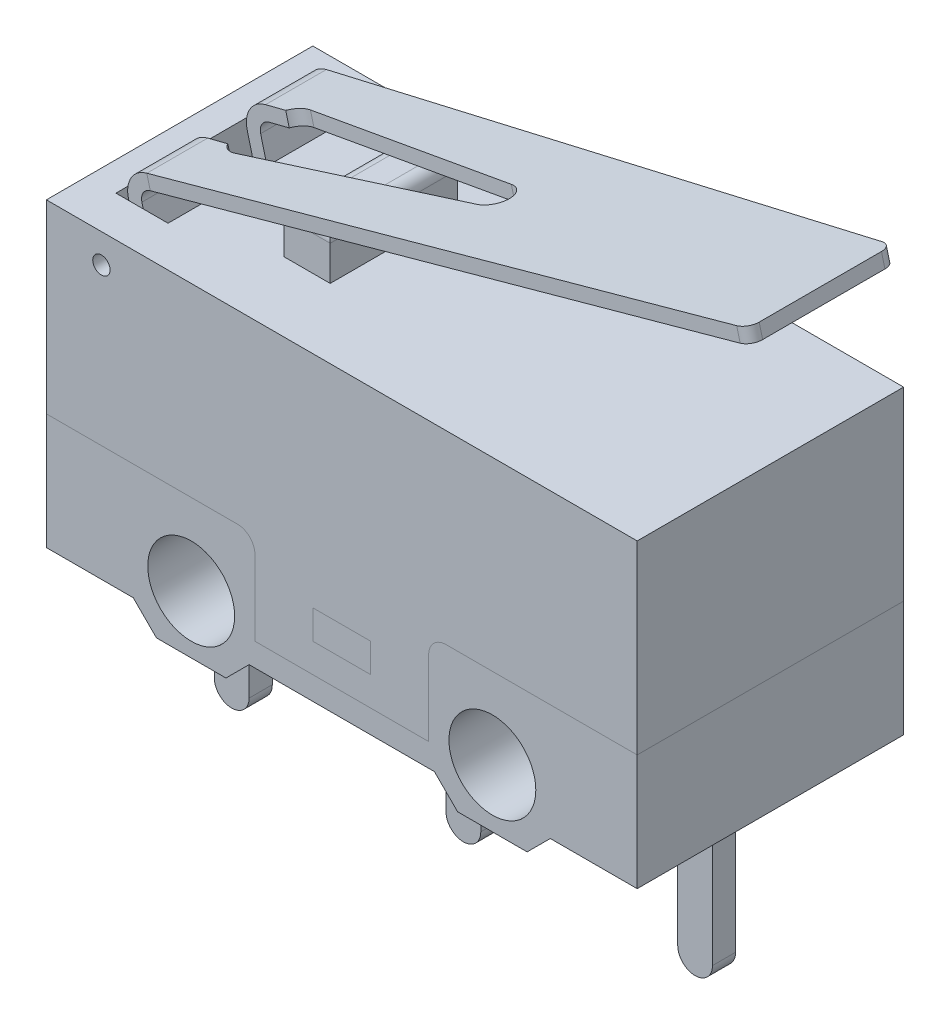
SolidWorks part; units mm, degrees
ref_plane "Front Plane" through (0, 0, 0) normal (0, 0, 1) x (1, 0, 0)
ref_plane "Top Plane" through (0, 0, 0) normal (0, 1, 0) x (1, 0, 0)
ref_plane "Right Plane" through (0, 0, 0) normal (1, 0, 0) x (0, 0, -1)
sketch "Sketch1" plane through (0, 0, 0) normal (0, 0, 1) x (1, 0, 0)
  line L0 (-4.572, -3.302) -> (-4.064, -3.81)
  line L1 (-6.477, 3.302) -> (6.477, 3.302)
  line L2 (-6.477, 3.302) -> (-6.477, -3.302)
  line L3 (-6.477, -3.302) -> (-4.572, -3.302)
  line L4 (6.477, 3.302) -> (6.477, -3.302)
  line L5 (-6.477, 3.302) -> (6.477, -3.302) construction
  line L6 (-6.477, -3.302) -> (6.477, 3.302) construction
  line L7 (-4.064, -3.81) -> (-2.54, -3.81)
  line L8 (-2.54, -3.81) -> (-2.032, -3.302)
  line L9 (2.032, -3.302) -> (2.54, -3.81)
  line L10 (2.54, -3.81) -> (4.064, -3.81)
  line L11 (4.064, -3.81) -> (4.572, -3.302)
  line L12 (0, 0) -> (0, -3.302) construction
  line L13 (-2.032, -3.302) -> (2.032, -3.302)
  line L14 (4.572, -3.302) -> (6.477, -3.302)
  line L15 (-3.302, -3.81) -> (-3.302, -3.302) construction
  line L16 (3.302, -3.81) -> (3.302, -3.302) construction
  circle A0 centre (3.302, -2.54) radius 0.9525
  circle A1 centre (-3.302, -2.54) radius 0.9525
  point P0 (0, 0)
  point P18 (-3.302, -3.81)
  point P19 (3.302, -3.81)
  dimension "D6" = 1.905
  dimension "D1" = 12.954
  dimension "D2" = 6.604
  dimension "D3" = 6.604
  dimension "D4" = 0.508
  dimension "D5" = 2.54
  dimension "D7" = 1.27
extrude "Boss-Extrude1" add sketch "Sketch1" along normal mid plane 5.842
sketch "Sketch2" plane through (0, 0, 2.921) normal (0, 0, 1) x (1, 0, 0)
  line L0 (-6.477, -0.762) -> (-2.286, -0.762)
  line L1 (-6.477, 3.302) -> (-6.477, -3.302) construction
  line L2 (-1.905, -1.143) -> (-1.905, -2.794)
  line L3 (-1.905, -2.794) -> (1.905, -2.794)
  line L4 (1.905, -2.794) -> (1.905, -1.143)
  line L5 (2.286, -0.762) -> (6.477, -0.762)
  line L6 (6.477, -3.302) -> (6.477, 3.302) construction
  line L7 (0, 0) -> (0, -2.794) construction
  line L8 (-6.477, -3.302) -> (-4.572, -3.302) construction
  line L9 (-2.032, -3.302) -> (2.032, -3.302) construction
  line L11 (-0.635, -1.524) -> (0.635, -1.524)
  line L12 (-0.635, -1.524) -> (-0.635, -2.159)
  line L13 (-0.635, -2.159) -> (0.635, -2.159)
  line L14 (0.635, -1.524) -> (0.635, -2.159)
  line L15 (-0.635, -1.524) -> (0.635, -2.159) construction
  line L16 (-0.635, -2.159) -> (0.635, -1.524) construction
  arc A0 (1.905, -1.143) -> (2.286, -0.762) centre (2.286, -1.143) cw
  arc A1 (-2.286, -0.762) -> (-1.905, -1.143) centre (-2.286, -1.143) cw
  point P22 (0, -1.8415)
  dimension "D4" = 0.381
  dimension "D1" = 2.54
  dimension "D2" = 0.508
  dimension "D3" = 3.81
  dimension "D5" = 1.27
  dimension "D6" = 0.635
  dimension "D7" = 0.635
split line "Split Line1"
sketch "Sketch3" plane through (6.477, 0, 0) normal (1, 0, 0) x (0, 0, -1)
  line L0 (-2.921, -0.762) -> (2.921, -0.762)
split line "Split Line2"
sketch "Sketch4" plane through (0, -3.302, 0) normal (0, -1, 0) x (1, 0, 0)
  line L0 (0, 0) -> (0, -0.254) construction
  line L1 (-5.461, 0.254) -> (-4.699, 0.254)
  line L2 (-5.461, 0.254) -> (-5.461, -0.254)
  line L3 (-5.461, -0.254) -> (-4.699, -0.254)
  line L4 (-4.699, 0.254) -> (-4.699, -0.254)
  line L5 (-5.461, 0.254) -> (-4.699, -0.254) construction
  line L6 (-5.461, -0.254) -> (-4.699, 0.254) construction
  line L7 (-0.381, 0.254) -> (0.381, 0.254)
  line L8 (-0.381, 0.254) -> (-0.381, -0.254)
  line L9 (-0.381, -0.254) -> (0.381, -0.254)
  line L10 (0.381, 0.254) -> (0.381, -0.254)
  line L11 (-0.381, 0.254) -> (0.381, -0.254) construction
  line L12 (-0.381, -0.254) -> (0.381, 0.254) construction
  line L13 (4.699, 0.254) -> (5.461, 0.254)
  line L14 (4.699, 0.254) -> (4.699, -0.254)
  line L15 (4.699, -0.254) -> (5.461, -0.254)
  line L16 (5.461, 0.254) -> (5.461, -0.254)
  line L17 (4.699, 0.254) -> (5.461, -0.254) construction
  line L18 (4.699, -0.254) -> (5.461, 0.254) construction
  point P0 (-5.08, 0)
  point P5 (0, 0)
  point P11 (5.08, 0)
  dimension "D1" = 0.762
  dimension "D2" = 0.508
  dimension "D3" = 10.16
extrude "Boss-Extrude2" add sketch "Sketch4" along normal blind 3.683
fillet "Fillet1" radius 0.381
sketch "Sketch5" plane through (0, 3.302, 0) normal (0, 1, 0) x (1, 0, 0)
  line L0 (-6.477, -2.921) -> (-6.477, 2.921) construction
  line L1 (-4.699, -2.032) -> (-5.842, -2.032)
  line L2 (-4.699, -2.032) -> (-4.699, 2.032)
  line L3 (-4.699, 2.032) -> (-5.842, 2.032)
  line L4 (-5.842, -2.032) -> (-5.842, 2.032)
  line L5 (-4.699, -2.032) -> (-5.842, 2.032) construction
  line L6 (-4.699, 2.032) -> (-5.842, -2.032) construction
  point P0 (-5.2705, 0)
  dimension "D1" = 1.143
  dimension "D2" = 4.064
  dimension "D3" = 0.635
extrude "Cut-Extrude1" cut sketch "Sketch5" against normal blind 1.27
sketch "Sketch7" plane through (0, 0, 0) normal (0, 0, 1) x (1, 0, 0)
  line L0 (-4.699, 3.302) -> (-5.842, 2.032) construction
  circle A0 centre (-5.2705, 2.667) radius 0.1905
  dimension "D1" = 0.381
extrude "Cut-Extrude2" cut sketch "Sketch7" against normal through all both and the other way through all
sketch "Sketch8" plane through (0, 0, 0) normal (0, 0, 1) x (1, 0, 0)
  line L0 (-2.794, 4.318) -> (-2.794, 3.302)
  line L1 (6.477, 3.302) -> (-6.477, 3.302) construction
  line L2 (-2.794, 3.302) -> (-1.778, 3.302)
  line L3 (-1.778, 3.302) -> (-1.778, 4.318)
  line L5 (-2.794, 4.318) -> (-1.778, 4.318)
  dimension "D1" = 1.016
  dimension "D2" = 3.683
  dimension "D3" = 1.016
extrude "Boss-Extrude3" add sketch "Sketch8" along normal mid plane 2.794 separate body
fillet "Fillet2" radius 0.254 4 edges at (-1.778, 4.318, 0) (-2.286, 4.318, 1.397) (-2.794, 4.318, 0) (-2.286, 4.318, -1.397)
sketch "Sketch9" plane through (0, 0, 0) normal (0, 0, 1) x (1, 0, 0)
  line L0 (-5.1285, 2.54) -> (-5.3353, 3.3523)
  line L1 (-5.1518, 3.6611) -> (7.6478, 6.92)
  line L2 (6.477, 3.302) -> (6.477, 6.6219) construction
  line L3 (-5.2705, 2.4765) -> (-5.2705, 2.667) construction
  line L4 (-5.2705, 2.54) -> (-5.1285, 2.54) construction
  circle A0 centre (-5.2705, 2.667) radius 0.1905 construction
  arc A2 (-2.54, 4.318) -> (-2.794, 4.064) centre (-2.54, 4.064) ccw construction
  arc A3 (-5.3353, 3.3523) -> (-5.1518, 3.6611) centre (-5.0892, 3.415) cw
  point P14 (-5.398, 3.5984)
  point P17 (-5.2705, 2.667)
  point P18 (-5.398, 3.5984)
  dimension "D3" = 0.254
  dimension "D1" = 1.0922
  dimension "D2" = 13.462
  dimension "D4" = 3.3199
  dimension "D5" = 0.0635
extrude "Extrude-Thin1" add sketch "Sketch9" along normal mid plane 4.826 separate body thin contours L0 A3 L1
ref_plane "Plane1" through (-0.9916, 3.8947, 0) normal (0.2467, -0.9691, 0) x (-0.9691, -0.2467, 0)
sketch "Sketch10" plane through (-0.9916, 3.8947, 0) normal (0.2467, -0.9691, 0) x (-0.9691, -0.2467, 0)
  line L0 (4.648, 1.9685) -> (4.0892, 1.9685)
  line L1 (4.0892, 1.9685) -> (-9.1188, 1.5875)
  line L2 (-9.1188, 1.5875) -> (-9.1188, -1.5875) construction
  line L3 (-9.1188, -1.5875) -> (4.0892, -1.9685)
  line L4 (4.648, -2.413) -> (4.648, 2.413) construction
  line L5 (4.0892, 2.413) -> (-9.1188, 2.413) construction
  line L6 (-9.1188, -2.413) -> (-9.1188, 2.413) construction
  line L8 (4.648, 2.413) -> (-9.1188, 2.413)
  line L9 (4.648, -2.413) -> (4.648, -1.9685)
  line L10 (-9.1188, -2.413) -> (4.648, -2.413)
  line L12 (4.0892, -1.9685) -> (4.648, -1.9685)
  line L13 (0, 0) -> (-9.1188, 0) construction
  line L15 (4.648, 1.9685) -> (4.648, 2.413)
  line L17 (4.0892, -2.413) -> (4.0892, 2.413) construction
  line L19 (4.648, -0.635) -> (3.632, -0.635)
  line L20 (3.632, -0.635) -> (3.632, 0.635) construction
  line L21 (3.632, 0.635) -> (4.648, 0.635)
  line L22 (4.648, 0) -> (0, 0) construction
  line L23 (3.2684, 0.824) -> (-1.7357, 0.3795)
  line L24 (3.2684, -0.824) -> (-1.7357, -0.3795)
  line L25 (-9.1188, 1.5875) -> (-9.1188, 2.413)
  line L26 (-9.1188, -1.5875) -> (-9.1188, -2.413)
  line L27 (4.648, 0.635) -> (4.648, -0.635)
  arc A0 (-1.7357, 0.3795) -> (-1.7357, -0.3795) centre (-1.702, 0) ccw
  arc A1 (3.632, 0.635) -> (3.2684, 0.824) centre (3.3021, 0.4445) ccw
  arc A2 (3.2684, -0.824) -> (3.632, -0.635) centre (3.3021, -0.4445) ccw
  dimension "D7" = 0.381
  dimension "D2" = 3.937
  dimension "D3" = 3.175
  dimension "D4" = 1.27
  dimension "D5" = 6.35
  dimension "D6" = 1.016
  dimension "D8" = 0.889
extrude "Cut-Extrude3" cut sketch "Sketch10" against normal blind 4.826
sketch "Sketch12" plane through (-0.9916, 3.8947, 0) normal (-0.2467, 0.9691, 0) x (0.9691, 0.2467, 0)
  line L4 (-4.3432, 0.635) -> (-4.648, 0.635)
  line L5 (-4.648, 0.635) -> (-4.648, -0.635)
  line L6 (-4.648, -0.635) -> (-4.3432, -0.635)
  line L8 (-4.3432, 0.635) -> (-4.648, 0.635)
  line L10 (-4.648, -0.635) -> (-4.3432, -0.635)
  line L18 (-4.3432, -0.635) -> (-4.3432, 0.635)
  line L19 (-4.3432, -0.635) -> (-4.3432, 0.635)
  line L21 (-4.648, 0.635) -> (-4.648, -0.635)
  dimension "D1" = 0
extrude "Cut-Extrude4" cut sketch "Sketch12" against normal up to next
fillet "Fillet3" radius 0.254 2 edges at (7.6102, 7.0677, -1.5875) (7.6102, 7.0677, 1.5875)
